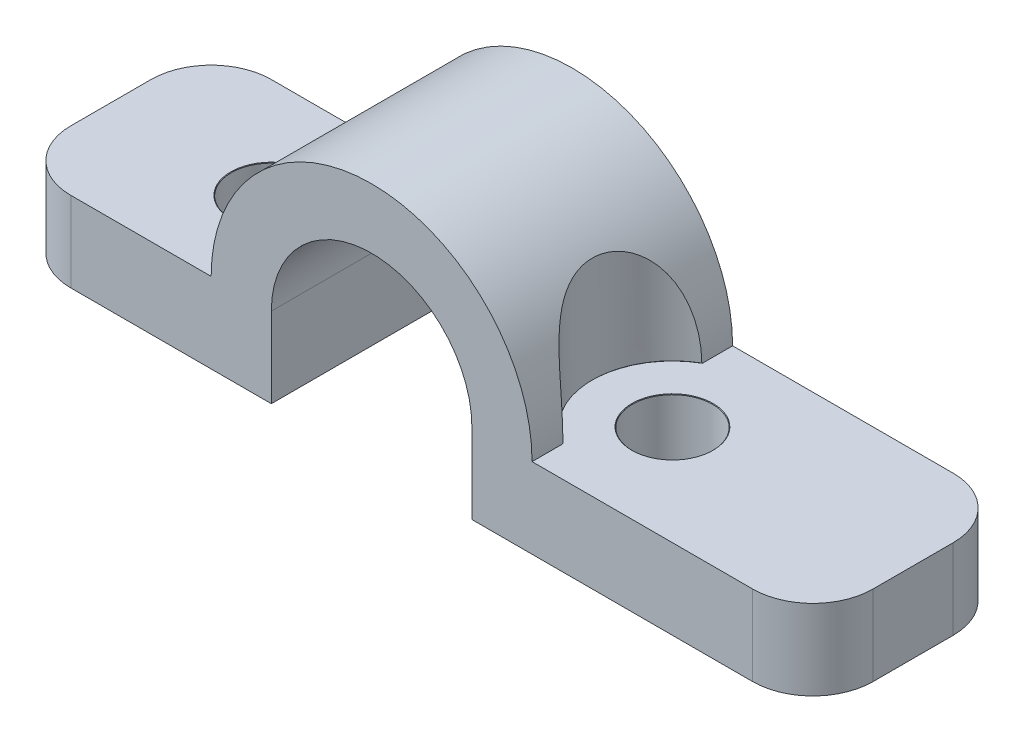
SolidWorks part; units mm, degrees
ref_plane "Front Plane" through (0, 0, 0) normal (0, 0, 1) x (1, 0, 0)
ref_plane "Top Plane" through (0, 0, 0) normal (0, 1, 0) x (1, 0, 0)
ref_plane "Right Plane" through (0, 0, 0) normal (1, 0, 0) x (0, 0, -1)
sketch "Sketch1" plane through (0, 0, 0) normal (0, 0, 1) x (1, 0, 0)
  line L0 (-19.7365, 0) -> (22.9614, 0) construction
  line L1 (0, -4.6937) -> (0, 10.6522) construction
  line L2 (-10, -5.2986) -> (-10, 10.1732) construction
  line L7 (-18, 0) -> (-5, 0)
  line L8 (-18, 0) -> (-18, 4)
  line L13 (-18, 4) -> (-8, 4)
  line L14 (-5, 0) -> (-5, 4)
  line L15 (8, 4) -> (22, 4)
  line L16 (22, 4) -> (22, 0)
  line L17 (22, 0) -> (5, 0)
  line L18 (5, 0) -> (5, 4)
  line L19 (10, -4.6937) -> (10, 8.7191) construction
  line L20 (-22.9642, 4) -> (23.822, 4) construction
  arc A2 (-8, 4) -> (8, 4) centre (0, 4) cw
  arc A3 (-5, 4) -> (5, 4) centre (0, 4) cw
  point P15 (0, 0)
  point P18 (0, 0)
  dimension "D1" = 8
  dimension "D4" = 3
  dimension "D6" = 5
  dimension "D2" = 10
  dimension "D3" = 10
  dimension "D5" = 3
  dimension "D7" = 40
  dimension "D8" = 4
extrude "Boss-Extrude1" add sketch "Sketch1" along normal blind 5 and the other way blind 5
sketch "Sketch3" plane through (0, 4, 0) normal (0, 1, 0) x (1, 0, 0)
  line L0 (-15.0178, 0) -> (18.7565, 0) construction
  line L1 (0, -7.206) -> (0, 5.9737) construction
  point P5 (10, 0)
  point P6 (-10, 0)
  dimension "D1" = 10
hole_wizard "Ø4.0mm Dowel Hole2" positions "Sketch6" profile "Sketch7" hole size "Ø4.0" standard "ANSI Metric" end condition through all
sketch "Sketch6" plane through (0, 4, 0) normal (0, 1, 0) x (1, 0, 0)
  point P0 (10, 0)
  point P3 (-10, 0)
sketch "Sketch7" plane through (10, 4, 0) normal (1, 0, 0) x (0, 0, 1)
  line L0 (0, 0) -> (0, 4)
  line L1 (0, 4) -> (2, 4)
  line L2 (2, 4) -> (2, 0.025)
  line L3 (2, 0.025) -> (2.025, 0)
  line L5 (2.025, 0) -> (0, 0)
  line L6 (-2, 0.025) -> (-2.025, 0) construction
  line L11 (0, -6.35) -> (0, 107.95) construction
  dimension "Thru Hole Dia." = 4
  dimension "Thru Hole Depth" = 4
  dimension "Near C'Sink Dia." = 4.05
  dimension "Near C'Sink Angle" = 90
fillet "Fillet1" radius 3 4 edges at (22, 2, 5) (-18, 2, 5) (22, 2, -5) (-18, 2, -5)
sketch "Sketch8" plane through (0, 4, 0) normal (0, 1, 0) x (1, 0, 0)
  point P0 (-10, 0)
  point P1 (10, 0)
hole_wizard "Ø8.0mm Dowel Hole1" positions "Sketch9" profile "Sketch10" hole size "Ø8.0" standard "ANSI Metric" end condition through all
sketch "Sketch9" plane through (0, 4, 0) normal (0, 1, 0) x (1, 0, 0)
  point P0 (-10, 0)
  point P3 (10, 0)
sketch "Sketch10" plane through (-10, 4, 0) normal (1, 0, 0) x (0, 0, -1)
  line L0 (0, 0) -> (0, 8)
  line L1 (0, 8) -> (4, 8)
  line L2 (4, 8) -> (4, 0.025)
  line L3 (4, 0.025) -> (4.025, 0)
  line L5 (4.025, 0) -> (0, 0)
  line L6 (-4, 0.025) -> (-4.025, 0) construction
  line L11 (0, -6.35) -> (0, 107.95) construction
  dimension "Thru Hole Dia." = 8
  dimension "Thru Hole Depth" = 8
  dimension "Near C'Sink Dia." = 8.05
  dimension "Near C'Sink Angle" = 90
